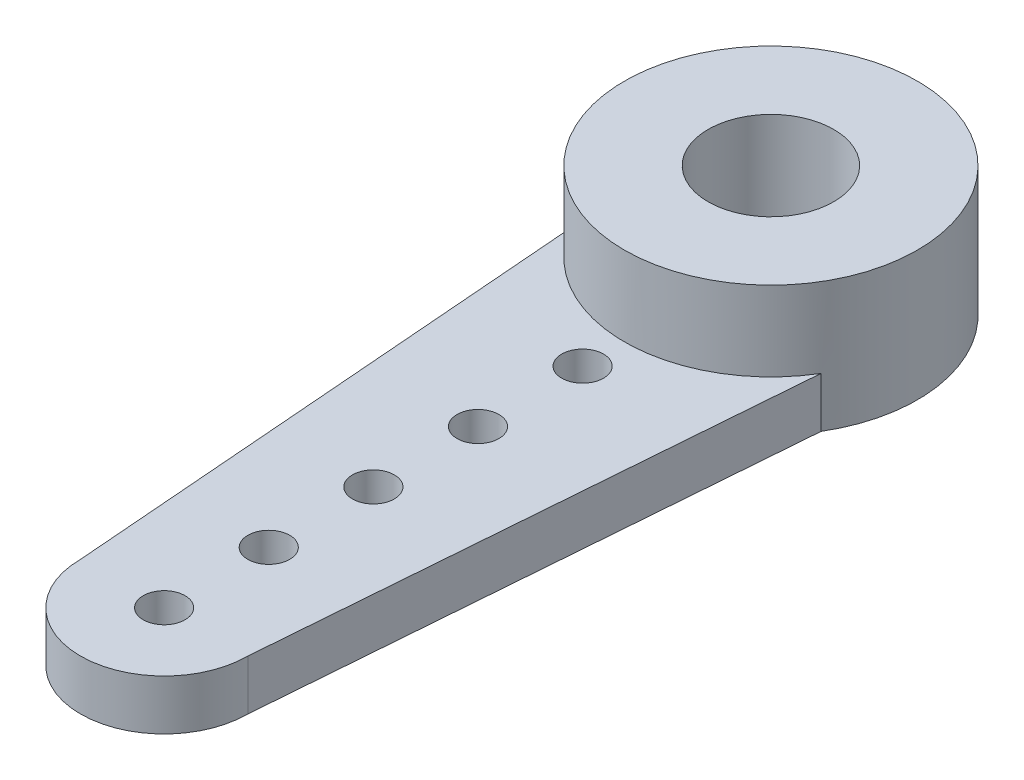
SolidWorks part; units mm, degrees
ref_plane "Front" through (0, 0, 0) normal (0, 0, 1) x (1, 0, 0)
ref_plane "Top" through (0, 0, 0) normal (0, 1, 0) x (1, 0, 0)
ref_plane "Right" through (0, 0, 0) normal (1, 0, 0) x (0, 0, -1)
sketch "草图1" plane through (0, 0, 0) normal (0, 1, 0) x (1, 0, 0)
  line L0 (-81.081, 0) -> (81.6093, 0) construction
  line L1 (0, 48.1996) -> (0, -46.0868) construction
  circle A0 centre (0, 0) radius 3.5
  dimension "D1" = 7
extrude "凸台-拉伸1" add sketch "草图1" along normal blind 3.1
sketch "草图2" plane through (0, 0, 0) normal (0, 1, 0) x (1, 0, 0)
  line L14 (-3, -1.8028) -> (-2, -14.5)
  line L15 (3, -1.8028) -> (2, -14.5)
  arc A1 (2, -14.5) -> (-2, -14.5) centre (0, -14.5) cw
  arc A3 (-3, -1.8028) -> (3, -1.8028) centre (0, 0) ccw
  dimension "D1" = 6
extrude "凸台-拉伸2" add sketch "草图2" along normal blind 1.2
sketch "草图3" plane through (0, 3.1, 0) normal (0, 1, 0) x (1, 0, 0)
  circle A0 centre (0, 0) radius 1.5
  dimension "D1" = 3
extrude "切除-拉伸1" cut sketch "草图3" against normal blind 3
sketch "草图4" plane through (0, 1.2, 0) normal (0, 1, 0) x (1, 0, 0)
  circle A0 centre (0, -14.5) radius 0.5
  circle A1 centre (0, -12) radius 0.5
  circle A2 centre (0, -9.5) radius 0.5
  circle A3 centre (0, -7) radius 0.5
  circle A4 centre (0, -4.5) radius 0.5
  dimension "D1" = 5
extrude "切除-拉伸2" cut sketch "草图4" against normal up to next
ref_axis "基准轴1" through (0, 0.1, 0) along (0, 1, 0)
ref_axis "基准轴2" through (0, 0, 14.5) along (0, 1, 0)
